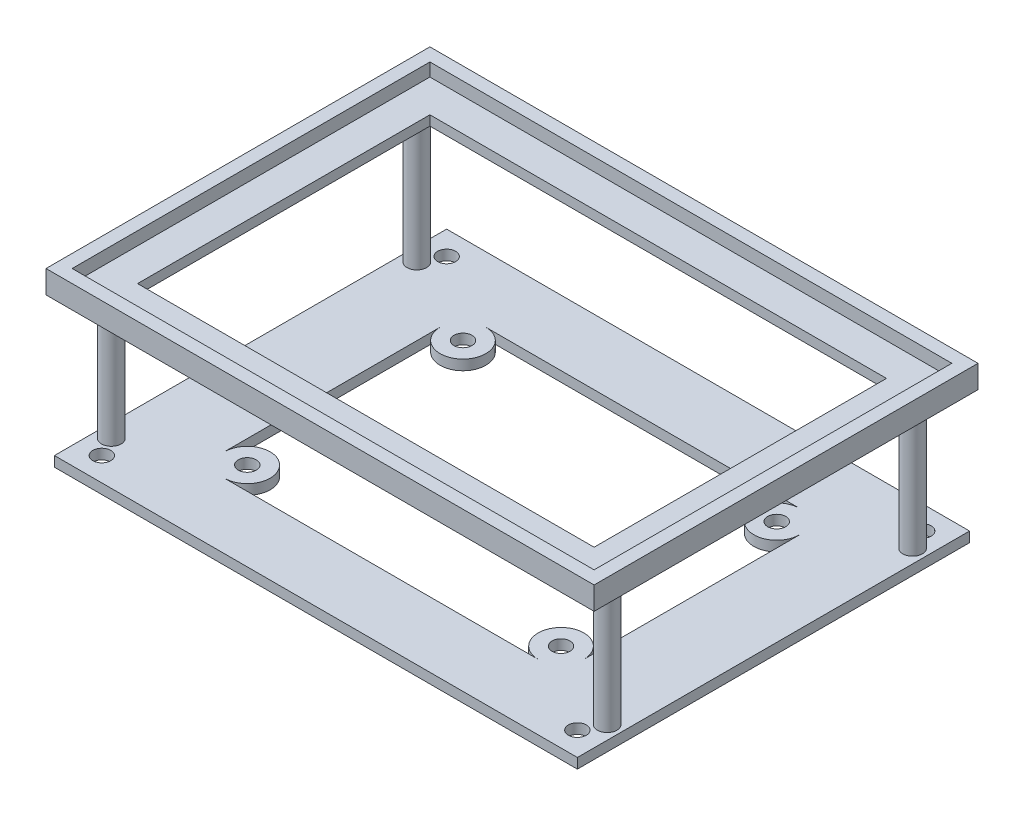
SolidWorks part; units mm, degrees
ref_plane "Front Plane" through (0, 0, 0) normal (0, 0, 1) x (1, 0, 0)
ref_plane "Top Plane" through (0, 0, 0) normal (0, 1, 0) x (1, 0, 0)
ref_plane "Right Plane" through (0, 0, 0) normal (1, 0, 0) x (0, 0, -1)
sketch "Sketch1" plane through (0, 0, 0) normal (0, 1, 0) x (1, 0, 0)
  line L0 (-36.375, 26.375) -> (-36.375, -26.375) construction
  line L1 (-40, -30) -> (40, -30)
  line L2 (-40, -30) -> (-40, 30)
  line L3 (-40, 30) -> (40, 30)
  line L4 (40, -30) -> (40, 30)
  line L5 (-40, -30) -> (40, 30) construction
  line L6 (-40, 30) -> (40, -30) construction
  line L7 (-36.375, 26.375) -> (36.375, 26.375) construction
  circle A4 centre (-36.375, 26.375) radius 1.375
  circle A5 centre (-36.375, -26.375) radius 1.375
  circle A6 centre (36.375, -26.375) radius 1.375
  circle A7 centre (36.375, 26.375) radius 1.375
  point P0 (0, 0)
  point P6 (0, 26.375)
  point P7 (-36.375, 0)
  dimension "D5" = 2.75
  dimension "D1" = 80
  dimension "D2" = 60
  dimension "D3" = 72.75
  dimension "D4" = 52.75
extrude "Boss-Extrude1" add sketch "Sketch1" along normal blind 1.55
sketch "Sketch2" plane through (0, 1.55, 0) normal (0, 1, 0) x (1, 0, 0)
  line L0 (-27.5, 20) -> (-24, 20)
  line L1 (-27.5, -20) -> (27.5, -20)
  line L2 (-27.5, -20) -> (-27.5, 20)
  line L3 (-27.5, 20) -> (27.5, 20)
  line L4 (27.5, -20) -> (27.5, 20)
  line L5 (-27.5, -20) -> (27.5, 20) construction
  line L6 (-27.5, 20) -> (27.5, -20) construction
  line L7 (0, 0) -> (-27.5, 0) construction
  line L8 (0, 0) -> (27.5, 0) construction
  line L9 (-24, -20) -> (24, -20)
  line L10 (0, 0) -> (0, 20)
  line L11 (0, 0) -> (0, -20)
  line L12 (-27.5, -16.5) -> (-27.5, 16.5)
  line L13 (-24, 20) -> (24, 20)
  line L14 (27.5, 16.5) -> (27.5, -16.5)
  line L15 (-27.5, 16.5) -> (-27.5, -16.5)
  line L16 (-24, -20) -> (24, -20)
  line L17 (27.5, -16.5) -> (27.5, 16.5)
  line L18 (-24, 20) -> (24, 20)
  circle A0 centre (-24, 16.5) radius 1.375
  circle A1 centre (24, 16.5) radius 1.375
  circle A2 centre (24, -16.5) radius 1.375
  circle A3 centre (-24, -16.5) radius 1.375
  circle A4 centre (-24, 16.5) radius 3.5
  circle A5 centre (-24, -16.5) radius 3.5
  circle A6 centre (24, -16.5) radius 3.5
  circle A7 centre (24, 16.5) radius 3.5
  point P0 (0, 0)
  dimension "D5" = 2.75
  dimension "D1" = 55
  dimension "D2" = 40
  dimension "D3" = 3.5
  dimension "D4" = 3.5
sketch "Sketch4" plane through (0, 1.55, 0) normal (0, 1, 0) x (1, 0, 0)
  line L0 (-27.5, -20) -> (27.5, -20) construction
  line L1 (-40, -30) -> (40, -30)
  line L2 (-40, -30) -> (-40, 30)
  line L3 (-40, 30) -> (40, 30)
  line L4 (40, -30) -> (40, 30)
  line L5 (-36.375, -22.75) -> (-27.5, -16.5)
  line L6 (-32.75, -26.375) -> (-24, -20)
  line L7 (0, 0) -> (0, -30) construction
  line L8 (0, 0) -> (40, 0) construction
  line L9 (36.375, -22.75) -> (27.5, -16.5)
  line L10 (32.75, -26.375) -> (24, -20)
  line L11 (32.75, 26.375) -> (24, 20)
  line L12 (36.375, 22.75) -> (27.5, 16.5)
  line L13 (-36.375, 22.75) -> (-27.5, 16.5)
  line L14 (-32.75, 26.375) -> (-24, 20)
  line L15 (-27.5, -16.5) -> (-27.5, 16.5)
  line L16 (-24, -20) -> (24, -20)
  line L17 (27.5, -16.5) -> (27.5, 16.5)
  line L18 (24, 20) -> (-24, 20)
  circle A0 centre (-24, -16.5) radius 3.5
  circle A1 centre (-36.375, -26.375) radius 3.625
  circle A2 centre (24, -16.5) radius 3.5
  circle A3 centre (36.375, -26.375) radius 3.625
  circle A4 centre (24, 16.5) radius 3.5
  circle A5 centre (36.375, 26.375) radius 3.625
  circle A6 centre (-24, 16.5) radius 3.5
  circle A7 centre (-36.375, 26.375) radius 3.625
ref_plane "Plane1" through (0, 1.55, 0) normal (0, 1, 0) x (1, 0, 0)
sketch "Sketch14" plane through (0, 1.55, 0) normal (0, 1, 0) x (1, 0, 0)
  line L0 (-27.5, -20) -> (27.5, -20) construction
  line L1 (-27.5, -20) -> (-27.5, 20) construction
  line L2 (-27.5, 20) -> (27.5, 20) construction
  line L3 (-27.5, 16.5) -> (-27.5, -16.5)
  line L4 (-24, 20) -> (24, 20)
  line L5 (27.5, 16.5) -> (27.5, -16.5)
  line L6 (-24, -20) -> (24, -20)
  arc A0 (27.5, -16.5) -> (24, -20) centre (24, -16.5) ccw
  arc A1 (-24, -20) -> (-27.5, -16.5) centre (-24, -16.5) ccw
  arc A2 (-24, 20) -> (-27.5, 16.5) centre (-24, 16.5) cw
  arc A3 (27.5, 16.5) -> (24, 20) centre (24, 16.5) cw
  circle A4 centre (-24, 16.5) radius 1.375
  circle A5 centre (24, 16.5) radius 1.375
  circle A6 centre (24, -16.5) radius 1.375
  circle A7 centre (-24, -16.5) radius 1.375
extrude "Cut-Extrude6" cut sketch "Sketch14" against normal through all contours L6 A0 L5 A3 L4 A2 L3 A1 | A6 | A5 | A7 | A4
ref_plane "Plane2" through (0, 21.55, 0) normal (0, 1, 0) x (1, 0, 0)
sketch "Sketch15" plane through (0, 21.55, 0) normal (0, 1, 0) x (1, 0, 0)
  line L0 (0, 0) -> (0, 20) construction
  line L1 (-39.925, -27.365) -> (39.925, -27.365)
  line L2 (-39.925, -27.365) -> (-39.925, 27.365)
  line L3 (-39.925, 27.365) -> (39.925, 27.365)
  line L4 (39.925, -27.365) -> (39.925, 27.365)
  line L5 (-39.925, -27.365) -> (39.925, 27.365) construction
  line L6 (-39.925, 27.365) -> (39.925, -27.365) construction
  line L7 (0, 0) -> (0, -20) construction
  line L8 (0, 0) -> (-27.5, 0) construction
  line L9 (0, 0) -> (27.5, 0) construction
  line L10 (-39.925, 27.365) -> (-34.1659, 27.365)
  line L12 (-41.925, -29.365) -> (41.925, -29.365)
  line L13 (-41.925, -29.365) -> (-41.925, 29.365)
  line L14 (-41.925, 29.365) -> (41.925, 29.365)
  line L15 (41.925, -29.365) -> (41.925, 29.365)
  line L16 (-41.925, -29.365) -> (41.925, 29.365) construction
  line L17 (-41.925, 29.365) -> (41.925, -29.365) construction
  line L18 (-34.925, -23.4071) -> (34.925, -23.4071)
  line L19 (-34.925, -23.4071) -> (-34.925, 23.4071)
  line L20 (-34.925, 23.4071) -> (34.925, 23.4071)
  line L21 (34.925, -23.4071) -> (34.925, 23.4071)
  line L22 (-34.925, -23.4071) -> (34.925, 23.4071) construction
  line L23 (-34.925, 23.4071) -> (34.925, -23.4071) construction
  point P0 (0, 0)
  dimension "D1" = 79.85
  dimension "D2" = 54.73
  dimension "D3" = 2
  dimension "D4" = 2
  dimension "D5" = 5
  dimension "D6" = 5
extrude "Boss-Extrude3" add sketch "Sketch15" along normal blind 3.5 separate body contours L13 L12 L15 L14 | L2 L1 L4 L3
sketch "Sketch16" plane through (0, 21.55, 0) normal (0, 1, 0) x (1, 0, 0)
  line L1 (-39.925, -27.365) -> (39.925, -27.365)
  line L2 (-39.925, -27.365) -> (-39.925, 27.365)
  line L3 (-39.925, 27.365) -> (39.925, 27.365)
  line L4 (39.925, -27.365) -> (39.925, 27.365)
  line L5 (-39.925, -27.365) -> (39.925, 27.365) construction
  line L6 (-39.925, 27.365) -> (39.925, -27.365) construction
  point P0 (0, 0)
extrude "Boss-Extrude4" add sketch "Sketch16" along normal blind 1.5
sketch "Sketch17" plane through (0, 23.05, 0) normal (0, 1, 0) x (1, 0, 0)
  line L0 (39.925, -27.365) -> (39.925, 27.365) construction
  line L1 (-34.925, -22.365) -> (34.925, -22.365)
  line L2 (-34.925, -22.365) -> (-34.925, 22.365)
  line L3 (-34.925, 22.365) -> (34.925, 22.365)
  line L4 (34.925, -22.365) -> (34.925, 22.365)
  line L5 (-34.925, -22.365) -> (34.925, 22.365) construction
  line L6 (-34.925, 22.365) -> (34.925, -22.365) construction
  line L7 (39.925, 27.365) -> (-39.925, 27.365) construction
  point P0 (0, 0)
  dimension "D1" = 5
  dimension "D2" = 5
extrude "Cut-Extrude7" cut sketch "Sketch17" against normal blind 7.5
sketch "Sketch18" plane through (0, 21.55, 0) normal (0, 1, 0) x (1, 0, 0)
  line L1 (0, 0) -> (0, -20) construction
  line L2 (0, 0) -> (27.5, 0) construction
  line L3 (-34.925, -22.365) -> (34.925, -22.365) construction
  circle A0 centre (-37.925, -23.365) radius 1.5
  circle A1 centre (37.925, -23.365) radius 1.5
  circle A2 centre (37.925, 23.365) radius 1.5
  circle A3 centre (-37.925, 23.365) radius 1.5
  dimension "D1" = 3
  dimension "D2" = 3
  dimension "D3" = 1
extrude "Boss-Extrude5" add sketch "Sketch18" against normal up to surface (20 mm away) up to face at (-24, 1.55, -15.125)
